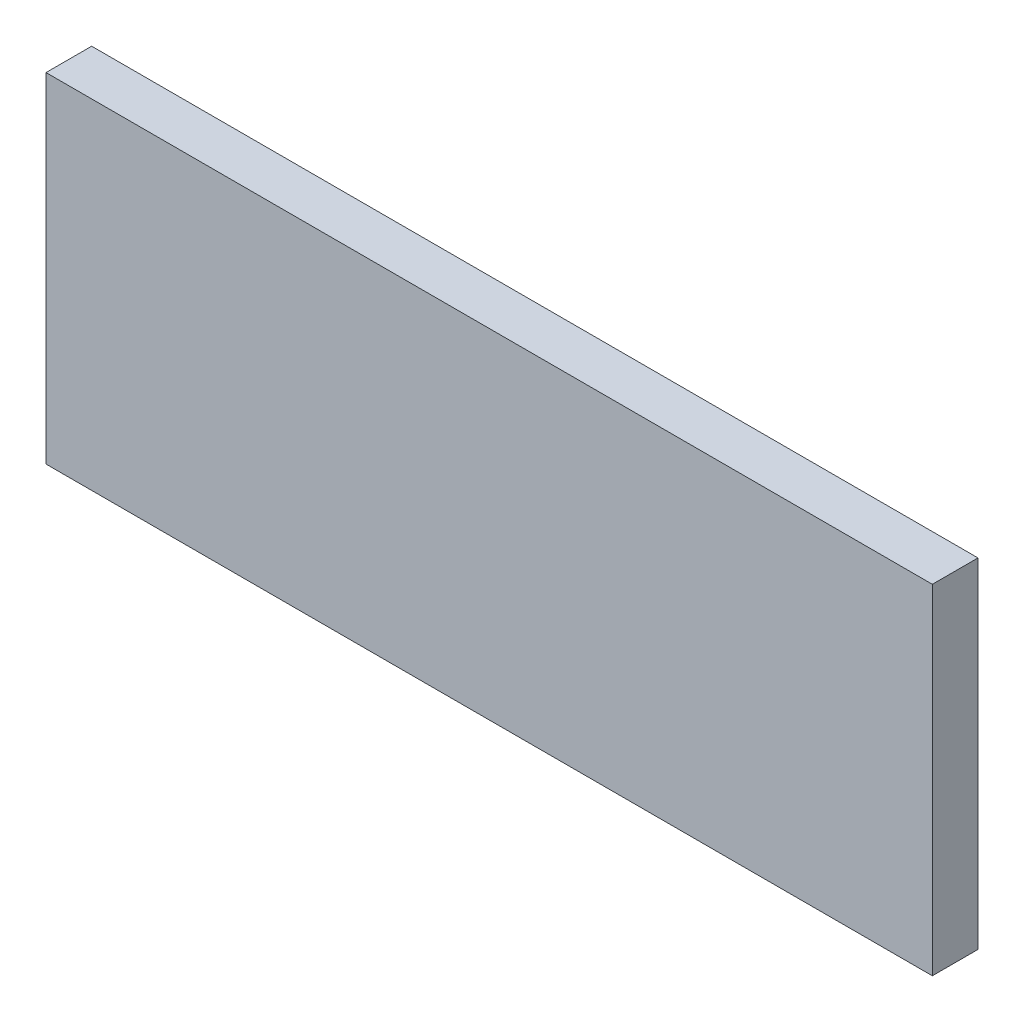
SolidWorks part; units mm, degrees
ref_plane "Front Plane" through (0, 0, 0) normal (0, 0, 1) x (1, 0, 0)
ref_plane "Top Plane" through (0, 0, 0) normal (0, 1, 0) x (1, 0, 0)
ref_plane "Right Plane" through (0, 0, 0) normal (1, 0, 0) x (0, 0, -1)
sketch "Sketch2" plane through (0, 0, 0) normal (0, 0, 1) x (1, 0, 0)
  line L1 (-46.228, -17.6847) -> (46.228, -17.6847)
  line L2 (-46.228, -17.6847) -> (-46.228, 17.6847)
  line L3 (-46.228, 17.6847) -> (46.228, 17.6847)
  line L4 (46.228, -17.6847) -> (46.228, 17.6847)
  line L5 (-46.228, -17.6847) -> (46.228, 17.6847) construction
  line L6 (-46.228, 17.6847) -> (46.228, -17.6847) construction
  point P0 (0, 0)
  dimension "D1" = 92.456
  dimension "D2" = 35.3695
extrude "Boss-Extrude1" add sketch "Sketch2" along normal blind 4.7625
